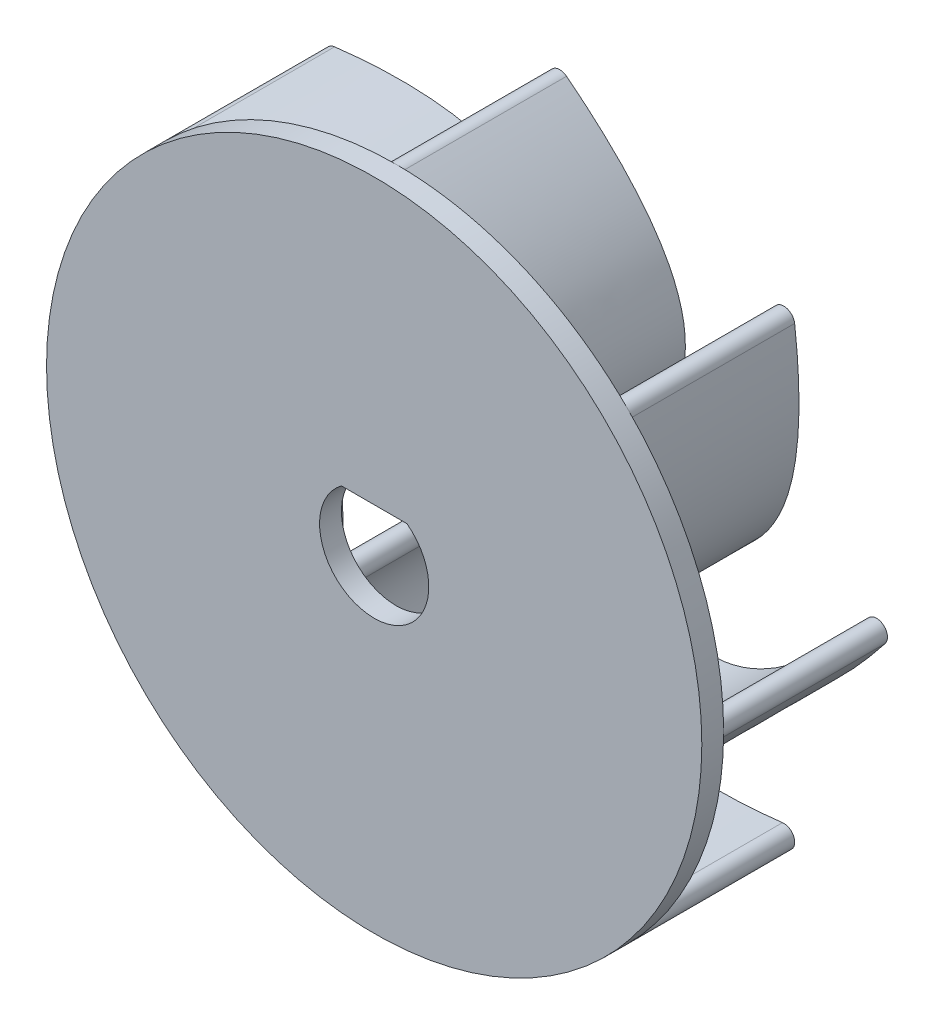
SolidWorks part; units mm, degrees
material "ABS"
ref_plane "前视基准面" through (0, 0, 0) normal (0, 0, 1) x (1, 0, 0)
ref_plane "上视基准面" through (0, 0, 0) normal (0, 1, 0) x (1, 0, 0)
ref_plane "右视基准面" through (0, 0, 0) normal (1, 0, 0) x (0, 0, -1)
other "Configuration Table"
sketch "草图1" plane through (0, 0, 0) normal (0, 0, 1) x (1, 0, 0)
  line L0 (-3, 4) -> (3, 4)
  circle A0 centre (0, 0) radius 30
  circle A1 centre (0, 0) radius 5
  dimension "D1" = 60
  dimension "D2" = 10
  dimension "D3" = 4
extrude "凸台-拉伸1" add sketch "草图1" along normal blind 2 contours A0 A1 | L0 A1 region at (0, 4.4036, 0) region at (-29.1515, 0, 0)
sketch "草图2" plane through (0, 0, 2) normal (0, 0, 1) x (1, 0, 0)
  line L0 (0, -5) -> (0, -30) construction
  line L1 (0, 0) -> (20.5061, -20.5061) construction
  line L2 (0, -13) -> (1.842, -19.8746) construction
  line L3 (0, -13) -> (2.5882, -22.6593) construction
  line L4 (2.5882, -22.6593) -> (20.5061, -20.5061) construction
  circle A0 centre (0, 0) radius 5 construction
  circle A1 centre (0, 0) radius 30 construction
  circle A2 centre (0, 0) radius 13 construction
  arc A4 (20.6254, -21.499) -> (20.3868, -19.5132) centre (20.5061, -20.5061) ccw
  arc A5 (-0.9659, -13.2588) -> (0.9659, -12.7412) centre (0, -13) cw
  spline S0 degree 2 poles (0, -13) (2.5882, -22.6593) (20.5061, -20.5061) knots 0 0 0 1 1 1 construction
  spline S1 degree 1 poles (-0.9659, -13.2588) (20.6254, -21.499) knots 0 0 1 1 construction
  spline S2 degree 2 poles (-0.9659, -13.2588) (-0.4389, -15.2401) (1.8472, -18.3565) (5.8529, -20.8549) (13.8151, -22.3276) (20.6254, -21.499) knots 0 0 0 0.1875 0.375 0.625 1 1 1
  spline S3 degree 1 poles (0.9659, -12.7412) (20.3868, -19.5132) knots 0 0 1 1 construction
  spline S4 degree 2 poles (0.9659, -12.7412) (1.4095, -14.3821) (3.2203, -16.8491) (6.5093, -18.9266) (13.7587, -20.2995) (20.3868, -19.5132) knots 0 0 0 0.1875 0.375 0.625 1 1 1
  dimension "D2" = 26
  dimension "D1" = 45
  dimension "D3" = 15
  dimension "D4" = 10
  dimension "D5" = 1
  dimension "D6" = 1
extrude "凸台-拉伸2" add sketch "草图2" against normal blind 17 contours S4 A4 S2 A5
pattern_circular "阵列(圆周)1" count 8 over 360 about axis through (0, 0, 2) along (0, 0, 1) of "凸台-拉伸2"
